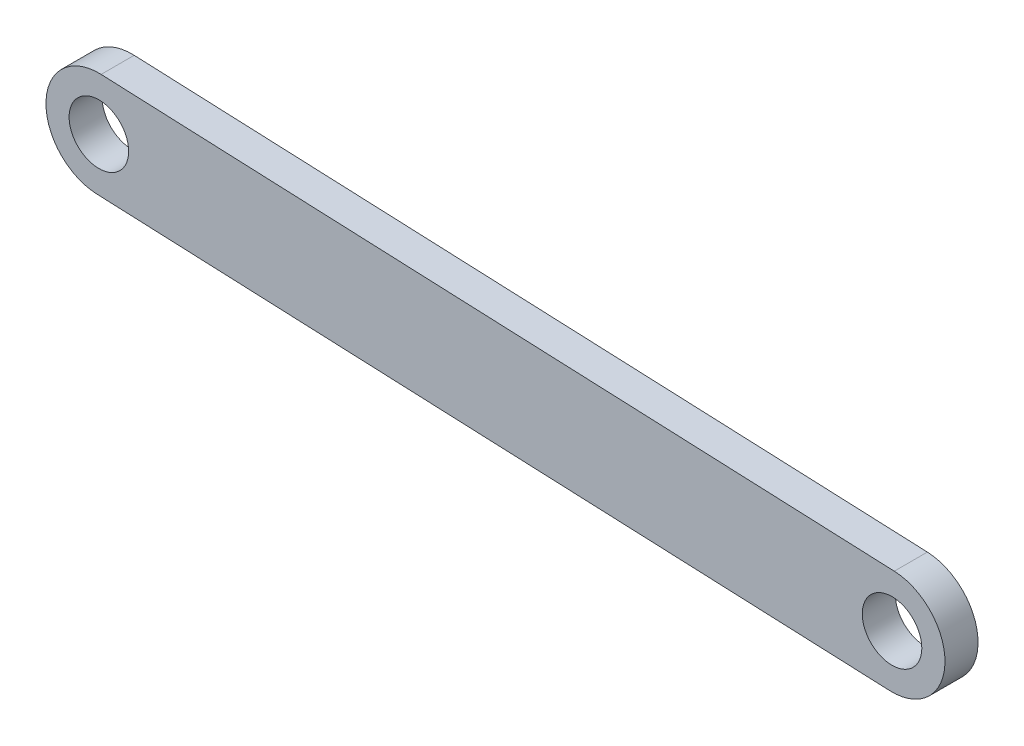
SolidWorks part; units mm, degrees
ref_plane "前视基准面" through (0, 0, 0) normal (0, 0, 1) x (1, 0, 0)
ref_plane "上视基准面" through (0, 0, 0) normal (0, 1, 0) x (1, 0, 0)
ref_plane "右视基准面" through (0, 0, 0) normal (1, 0, 0) x (0, 0, -1)
sketch "草图1" plane through (0, 0, 0) normal (0, 0, 1) x (1, 0, 0)
  line L0 (150.978, 33.8432) -> (270.8701, 28.7572) construction
  line L1 (151.317, 41.8361) -> (271.2092, 36.75)
  line L2 (150.6389, 25.8504) -> (270.5311, 20.7644)
  arc A0 (151.317, 41.8361) -> (150.6389, 25.8504) centre (150.978, 33.8432) ccw
  arc A1 (270.5311, 20.7644) -> (271.2092, 36.75) centre (270.8701, 28.7572) ccw
  circle A2 centre (150.978, 33.8432) radius 4.5
  circle A3 centre (270.8701, 28.7572) radius 4.5
  point P3 (210.924, 31.3002)
  dimension "D1" = 9
  dimension "D2" = 9
  dimension "D3" = 8
  dimension "D4" = 120
extrude "凸台-拉伸1" add sketch "草图1" along normal blind 5
